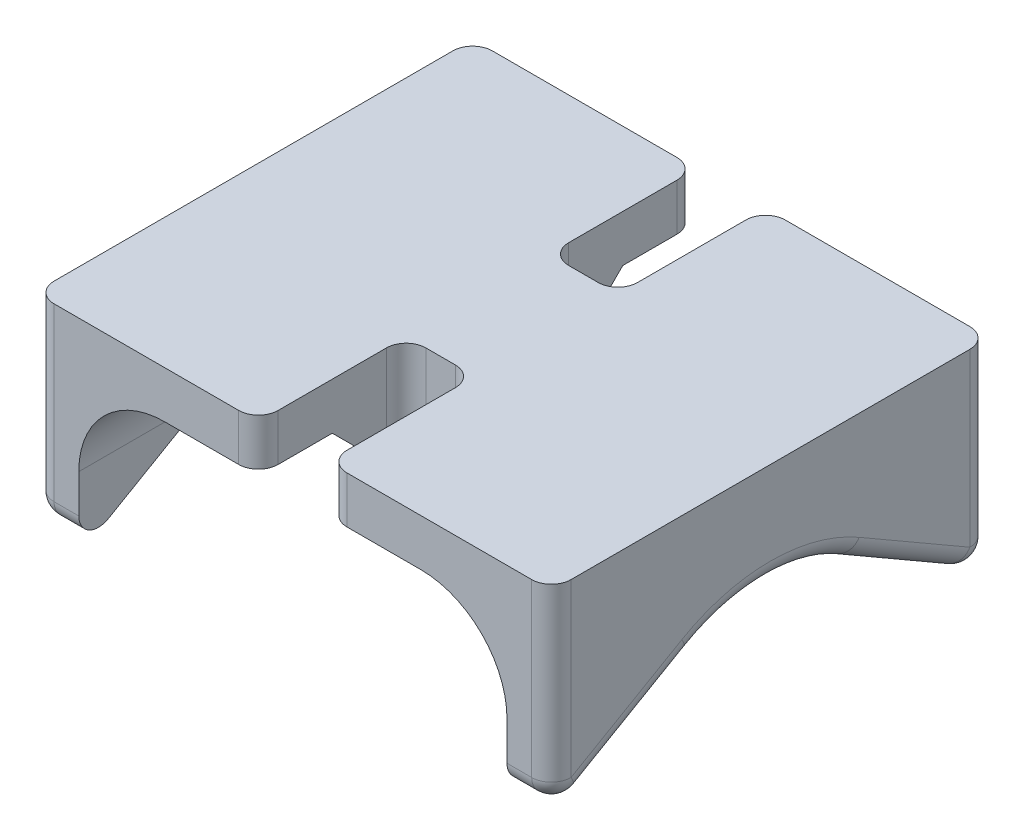
SolidWorks part; units mm, degrees
note: '?' marks a value the reader was unsure of.
material "ABS"
ref_plane "Front Plane" through (0, 0, 0) normal (0, 0, 1) x (1, 0, 0)
ref_plane "Top Plane" through (0, 0, 0) normal (0, 1, 0) x (1, 0, 0)
ref_plane "Right Plane" through (0, 0, 0) normal (1, 0, 0) x (0, 0, -1)
sketch "Sketch2" plane through (0, 0, 0) normal (0, 0, 1) x (1, 0, 0)
  line L0 (0, 0) -> (57.6033, 0) construction
  line L1 (0, 0) -> (6.6005, 6.6005) construction
  line L4 (0, 0) -> (0, 21.964) construction
  line L5 (-6.6005, 6.6005) -> (6.6005, 6.6005) construction
  line L8 (0, 0) -> (63.5, 109.9852) construction
  line L9 (-6.6005, 13.201) -> (1.5205, 13.201)
  line L10 (-6.6005, 0) -> (11.6805, 0)
  line L11 (6.6005, 16.1339) -> (1.5205, 13.201)
  line L12 (6.6005, 13.201) -> (0.8843, 9.9007) construction
  line L13 (0.8843, 9.9007) -> (0.8843, 3.3002) construction
  line L14 (0.8843, 3.3002) -> (6.6005, 0) construction
  line L15 (6.6005, 0) -> (12.3167, 3.3002) construction
  line L16 (12.3167, 3.3002) -> (12.3167, 9.9007) construction
  line L17 (12.3167, 9.9007) -> (6.6005, 13.201) construction
  line L20 (11.6805, 0) -> (14.8567, 1.8338)
  line L21 (14.8567, 1.8338) -> (14.8567, 11.3672)
  line L22 (14.8567, 11.3672) -> (6.6005, 16.1339)
  line L23 (-1.6557, 1.8338) -> (6.6005, -2.9329) construction
  line L24 (6.6005, -2.9329) -> (14.8567, 1.8338) construction
  line L26 (6.6005, 16.1339) -> (-1.6557, 11.3672) construction
  line L27 (-1.6557, 11.3672) -> (-1.6557, 1.8338) construction
  circle A0 centre (0, 0) radius 127 construction
  circle A7 centre (6.6005, 6.6005) radius 1.4605 construction
  circle A8 centre (-6.6005, 6.6005) radius 1.4605 construction
  arc A9 (-6.6005, 13.201) -> (-6.6005, 0) centre (-6.6005, 6.6005) ccw
  circle A11 centre (6.6005, 6.6005) radius 5.7162 construction
  point P7 (0, 6.6005)
  dimension "D1" = 254
  dimension "D2" = 9.3345
  dimension "D3" = 45
  dimension "D4" = 2.921
  dimension "D5" = 60
sketch "Sketch3" plane through (0, 0, 0) normal (0, 1, 0) x (1, 0, 0)
  line L0 (0, 0) -> (0, 56.834) construction
ref_plane "Plane1" through (0, 0, 0) normal (0.866, -0.5, 0) x (0, 0, -1)
sketch "Sketch16" plane through (0, 0, 0) normal (0.866, -0.5, 0) x (0, 0, -1)
  line L0 (0, 0) -> (0, 139.7) construction
  line L2 (0, 139.7) -> (63.5, 139.7) construction
  point P4 (63.5, 139.7)
  dimension "D1" = 139.7
  dimension "D2" = 63.5
ref_plane "Plane2" through (69.85, 120.9837, 0) normal (-0.5, -0.866, 0) x (0, 0, -1)
ref_plane "Plane3" through (0, 0, 3.175) normal (0, 0, 1) x (1, 0, 0)
ref_plane "Plane4" through (0, 0, 0) normal (-0.5, -0.866, 0) x (-0.866, 0.5, 0)
ref_plane "Plane5" through (0, 13.462, 0) normal (0, 1, 0) x (1, 0, 0)
ref_axis "Axis1" through (7.7723, 13.462, -59.6757) along (0, 0, 1)?
sketch "Sketch23" plane through (0, 13.462, 0) normal (0, 1, 0) x (1, 0, 0)
  line L0 (0, 0) -> (0, 12.7) construction
  line L1 (0, 0) -> (0, 56.834) construction
  line L3 (-13.335, 1.397) -> (13.335, 1.397)
  line L4 (-13.335, 1.397) -> (-13.335, 24.003)
  line L5 (-13.335, 24.003) -> (13.335, 24.003)
  line L6 (13.335, 1.397) -> (13.335, 24.003)
  line L7 (-13.335, 1.397) -> (13.335, 24.003) construction
  line L8 (-13.335, 24.003) -> (13.335, 1.397) construction
  dimension "D1" = 12.7
  dimension "D2" = 22.606
  dimension "D3" = 26.67
extrude "Boss-Extrude8" add sketch "Sketch23" against normal blind 13.208 separate body
sketch "Sketch25" plane through (0, 0, -24.003) normal (0, 0, -1) x (-1, 0, 0)
  line L0 (0, 13.462) -> (0, 0.254) construction
  line L1 (0, 0) -> (0, 21.964) construction
  line L2 (1.778, 13.462) -> (1.778, 11.0455)
  line L3 (-1.778, 13.462) -> (-1.778, 11.0455)
  line L4 (-6.6005, 11.0455) -> (-1.778, 11.0455)
  line L5 (13.335, 13.462) -> (-13.335, 13.462)
  line L6 (-13.335, 13.462) -> (-13.335, 0.254)
  line L7 (-13.335, 0.254) -> (13.335, 0.254)
  line L8 (13.335, 0.254) -> (13.335, 13.462)
  line L12 (-11.0455, 0.254) -> (11.0455, 0.254)
  line L15 (-11.0455, 6.6005) -> (-11.0455, 0.254)
  line L16 (0, 13.462) -> (0, 31.7164) construction
  line L17 (6.6005, 11.0455) -> (1.778, 11.0455)
  line L18 (11.0455, 6.6005) -> (11.0455, 0.254)
  arc A0 (-6.6005, 11.0455) -> (-11.0455, 6.6005) centre (-6.6005, 6.6005) ccw
  arc A1 (1.778, 13.462) -> (-1.778, 13.462) centre (0, 13.462) ccw
  arc A3 (6.6005, 11.0455) -> (11.0455, 6.6005) centre (6.6005, 6.6005) cw
  point P12 (0, 6.858)
  dimension "D2" = 8.89
  dimension "D1" = 0
extrude "Cut-Extrude1" cut sketch "Sketch25" against normal blind 7.62
sketch "Sketch27" plane through (0, 0, 0) normal (1, 0, 0) x (0, 0, -1)
  line L0 (0, 0) -> (12.7, 0) construction
  line L1 (0, 0) -> (56.834, 0) construction
  circle A0 centre (12.7, 0) radius 8.128
  dimension "D2" = 16.256
  dimension "D1" = 12.7
extrude "Cut-Extrude3" cut sketch "Sketch27" against normal mid plane 76.2
sketch "Sketch28" plane through (13.335, 0, 0) normal (1, 0, 0) x (0, 0, -1)
  line L0 (1.397, 2.8596) -> (8.636, 7.0391)
  line L1 (1.397, 0.254) -> (1.397, 13.462) construction
  line L2 (24.003, 2.8596) -> (16.764, 7.0391)
  line L3 (24.003, 0.254) -> (24.003, 13.462) construction
  line L4 (1.397, 2.8596) -> (1.397, 0.254)
  line L5 (1.397, 0.254) -> (24.003, 0.254)
  line L6 (24.003, 0.254) -> (24.003, 2.8596)
  arc A2 (20.824, 0.254) -> (4.576, 0.254) centre (12.7, 0) ccw construction
  arc A3 (16.764, 7.0391) -> (8.636, 7.0391) centre (12.7, 0) ccw
  dimension "D1" = 60
  dimension "D2" = 60
extrude "Cut-Extrude4" cut sketch "Sketch28" against normal blind 76.2 contours L0 A3 L2 L6 L5 L4
ref_plane "Plane6" through (0, 0, -12.7) normal (0, 0, 1) x (1, 0, 0)
mirror "Mirror1" about plane through (0, 0, -12.7) normal (0, 0, 1) of "Cut-Extrude1"
chamfer "Chamfer1" distance 3.81 angle 45 4 edges at (-4.1892, 11.0455, -16.383) (4.1892, 11.0455, -16.383) (-4.1892, 11.0455, -9.017) (4.1892, 11.0455, -9.017)
fillet "Fillet1" radius 1.016 4 edges at (12.1902, 2.8596, -1.397) (-12.1902, 2.8596, -1.397) (12.1902, 2.8596, -24.003) (-12.1902, 2.8596, -24.003)
fillet "Fillet2" radius 1.016 8 edges at (1.778, 10.3538, -9.017) (-1.778, 10.3538, -9.017) (1.778, 12.2537, -1.397) (-1.778, 12.2537, -1.397) (1.778, 10.3538, -16.383) (-1.778, 10.3538, -16.383) (-1.778, 12.2537, -24.003) (1.778, 12.2537, -24.003)
fillet "Fillet4" radius 1.016 14 edges at (-13.335, 9.0407, -1.397) (-13.335, 3.7395, -1.905) (-13.335, 5.3893, -5.7785) (-13.335, 8.128, -12.7) (-13.335, 5.3893, -19.6215) (-13.335, 3.7395, -23.495) (13.335, 9.0407, -1.397) (13.335, 3.7395, -1.905) (13.335, 5.3893, -5.7785) (13.335, 8.128, -12.7) (13.335, 5.3893, -19.6215) (13.335, 3.7395, -23.495) (-13.335, 9.0407, -24.003) (13.335, 9.0407, -24.003)
